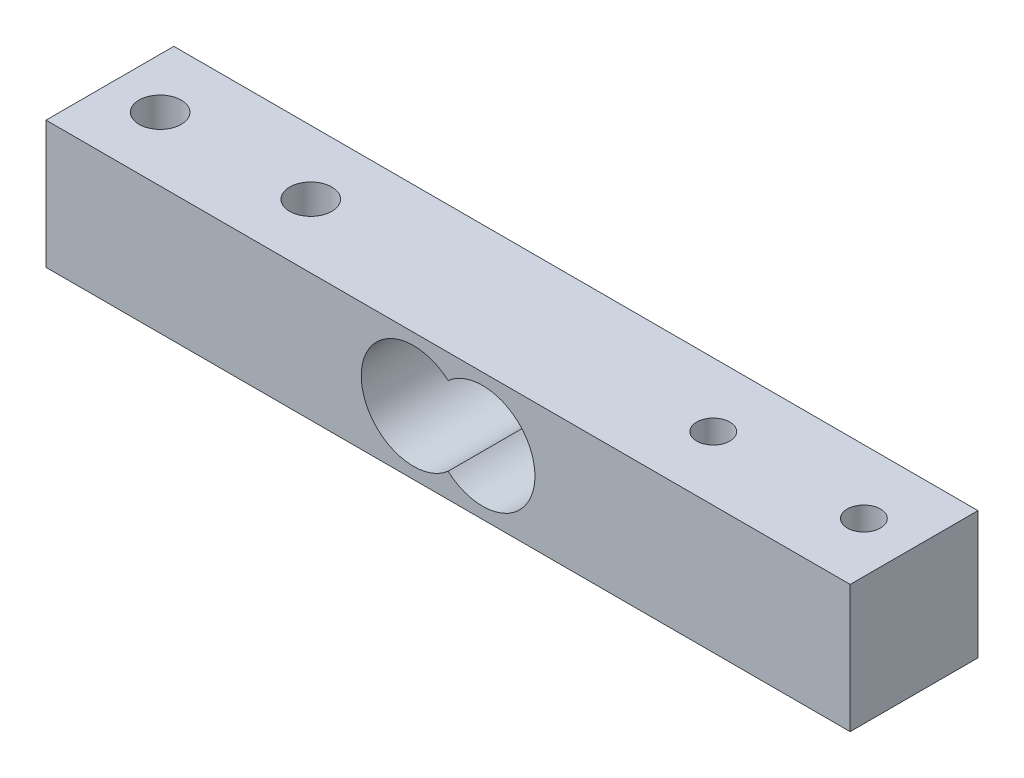
SolidWorks part; units mm, degrees
material "AISI 304"
ref_plane "Front Plane" through (0, 0, 0) normal (0, 0, 1) x (1, 0, 0)
ref_plane "Top Plane" through (0, 0, 0) normal (0, 1, 0) x (1, 0, 0)
ref_plane "Right Plane" through (0, 0, 0) normal (1, 0, 0) x (0, 0, -1)
sketch "Sketch1" plane through (0, 0, 0) normal (0, 0, 1) x (1, 0, 0)
  line L1 (40.04, 6.35) -> (-40.04, 6.35)
  line L2 (40.04, 6.35) -> (40.04, -6.35)
  line L3 (40.04, -6.35) -> (-40.04, -6.35)
  line L4 (-40.04, 6.35) -> (-40.04, -6.35)
  line L5 (40.04, 6.35) -> (-40.04, -6.35) construction
  line L6 (40.04, -6.35) -> (-40.04, 6.35) construction
  point P0 (0, 0)
  dimension "D1" = 80.08
  dimension "D2" = 12.7
extrude "Boss-Extrude1" add sketch "Sketch1" along normal blind 12.73
hole_wizard "M5x0.8 Tapped Hole1" positions "Sketch4" profile "Sketch3" tap size "M5x0.8" standard "ANSI Metric" end condition through all
sketch "Sketch4" plane through (0, 6.35, 0) normal (0, 1, 0) x (1, 0, 0)
  line L0 (-40.04, -12.73) -> (-40.04, 0) construction
  line L1 (-35.04, -6.365) -> (-40.04, -6.365) construction
  point P0 (-35.04, -6.365)
  point P2 (-20.04, -6.365)
  dimension "D1" = 15
  dimension "D2" = 5
sketch "Sketch3" plane through (-35.04, 6.35, 6.365) normal (1, 0, 0) x (0, 0, 1)
  line L0 (0, 0) -> (0, 12.7)
  line L1 (0, 12.7) -> (2.1, 12.7)
  line L2 (2.1, 12.7) -> (2.1, 0)
  line L5 (2.1, 0) -> (0, 0)
  line L11 (0, -6.35) -> (0, 107.95) construction
  dimension "Thru Tap Drill Dia." = 4.2
  dimension "Thru Tap Drill Depth" = 12.7
cosmetic thread "Hole Thread1" parameters "D2"=5
cosmetic thread "Hole Thread2" parameters "D2"=5
hole_wizard "M4x0.7 Tapped Hole1" positions "Sketch6" profile "Sketch5" tap size "M4x0.7" standard "ANSI Metric" end condition through all
sketch "Sketch6" plane through (0, 6.35, 0) normal (0, 1, 0) x (1, 0, 0)
  line L0 (40.04, -12.73) -> (40.04, 0) construction
  line L1 (35.04, -6.365) -> (40.04, -6.365) construction
  point P0 (20.04, -6.365)
  point P2 (35.04, -6.365)
  dimension "D1" = 15
  dimension "D2" = 5
sketch "Sketch5" plane through (20.04, 6.35, 6.365) normal (1, 0, 0) x (0, 0, 1)
  line L0 (0, 0) -> (0, 12.7)
  line L1 (0, 12.7) -> (1.65, 12.7)
  line L2 (1.65, 12.7) -> (1.65, 0)
  line L5 (1.65, 0) -> (0, 0)
  line L11 (0, -6.35) -> (0, 107.95) construction
  dimension "Thru Tap Drill Dia." = 3.3
  dimension "Thru Tap Drill Depth" = 12.7
cosmetic thread "Hole Thread3" parameters "D2"=4
cosmetic thread "Hole Thread4" parameters "D2"=4
sketch "Sketch7" plane through (0, 0, 12.73) normal (0, 0, 1) x (1, 0, 0)
  line L0 (0, 6.35) -> (0, -6.35) construction
  line L1 (40.04, 6.35) -> (-40.04, 6.35) construction
  line L2 (-40.04, -6.35) -> (40.04, -6.35) construction
  line L3 (-3.44, 0) -> (3.44, 0) construction
  circle A0 centre (-3.44, 0) radius 5.21
  circle A1 centre (3.44, 0) radius 5.21
  dimension "D1" = 10.42
  dimension "D2" = 17.3
extrude "Cut-Extrude1" cut sketch "Sketch7" against normal blind 12.73 contours A1 A0 | A0 A1 | A0 A1 region at (0, 0, 12.73) region at (4.4398, 0, 12.73) region at (-4.4398, 0, 12.73)
